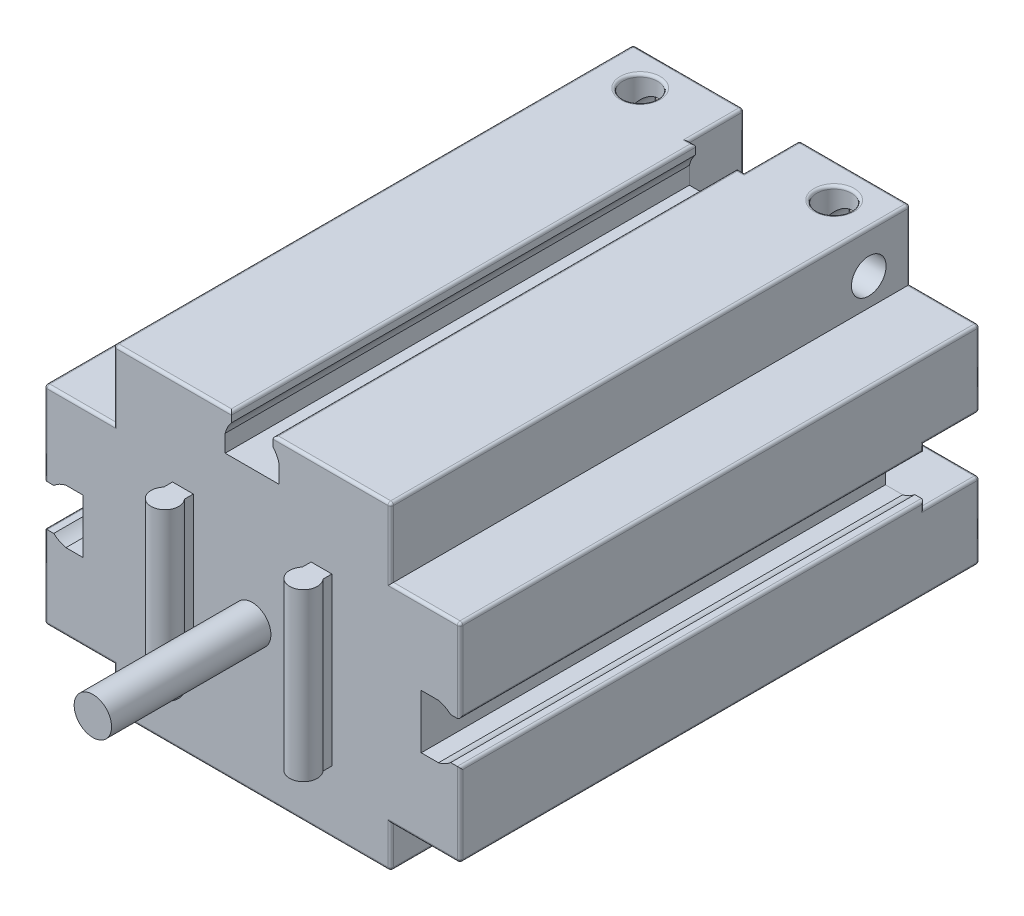
SolidWorks part; units mm, degrees
ref_plane "前视基准面" through (0, 0, 0) normal (0, 0, 1) x (1, 0, 0)
ref_plane "上视基准面" through (0, 0, 0) normal (0, 1, 0) x (1, 0, 0)
ref_plane "右视基准面" through (0, 0, 0) normal (1, 0, 0) x (0, 0, -1)
sketch "草图1" plane through (0, 0, 0) normal (0, 0, 1) x (1, 0, 0)
  line L0 (-15, 3) -> (-10, 3)
  line L1 (-10, 0) -> (10, 0)
  line L2 (-15, 3) -> (-15, 18)
  line L3 (-10, 23) -> (10, 23)
  line L4 (15, 3) -> (15, 18)
  line L5 (-10, 3) -> (-10, 0)
  line L6 (15, 3) -> (10, 3)
  line L7 (10, 3) -> (10, 0)
  line L8 (-10, 23) -> (-10, 18)
  line L9 (-10, 18) -> (-15, 18)
  line L10 (10, 23) -> (10, 18)
  line L11 (10, 18) -> (15, 18)
extrude "凸台-拉伸1" add sketch "草图1" against normal blind 37.5
sketch "草图3" plane through (0, 0, -37.5) normal (0, 0, -1) x (-1, 0, 0)
  line L0 (-15, 3) -> (-15, 18) construction
  line L1 (-15, 12.5) -> (-11, 12.5)
  line L2 (-15, 12.5) -> (-15, 8.5)
  line L3 (-15, 8.5) -> (-11, 8.5)
  line L4 (-11, 12.5) -> (-11, 8.5)
  line L5 (0, 24.5231) -> (0, -1.6726) construction
  line L6 (11, 12.5) -> (11, 8.5)
  line L7 (15, 8.5) -> (11, 8.5)
  line L8 (15, 12.5) -> (15, 8.5)
  line L9 (15, 12.5) -> (11, 12.5)
  line L10 (-10, 23) -> (10, 23) construction
  line L11 (-2, 23) -> (2, 23)
  line L12 (-2, 23) -> (-2, 19)
  line L13 (-2, 19) -> (2, 19)
  line L14 (2, 23) -> (2, 19)
extrude "切除-拉伸1" cut sketch "草图3" against normal blind 4
sketch "草图4" plane through (0, 0, 0) normal (0, 0, 1) x (1, 0, 0)
  line L0 (-1.5, 23) -> (-1.5, 22.3229)
  line L1 (10, 23) -> (-10, 23) construction
  line L2 (1.5, 23) -> (1.5, 22.3229)
  line L3 (-1.95, 20.2) -> (1.95, 20.2)
  line L4 (-1.95, 20.2) -> (-1.95, 21.4444)
  line L5 (1.95, 20.2) -> (1.95, 21.4444)
  line L6 (-1.5, 23) -> (1.5, 23)
  line L7 (-15, 9) -> (-14.3229, 9)
  line L8 (-15, 18) -> (-15, 3) construction
  line L9 (-15, 12) -> (-14.3229, 12)
  line L10 (-12.2, 8.55) -> (-13.4444, 8.55)
  line L11 (-12.2, 12.45) -> (-13.4444, 12.45)
  line L12 (-15, 9) -> (-15, 12)
  line L13 (-12.2, 8.55) -> (-12.2, 12.45)
  line L14 (0, 23.968) -> (0, -1.0844) construction
  line L15 (12.2, 8.55) -> (12.2, 12.45)
  line L16 (15, 9) -> (15, 12)
  line L17 (12.2, 12.45) -> (13.4444, 12.45)
  line L18 (12.2, 8.55) -> (13.4444, 8.55)
  line L19 (15, 12) -> (14.3229, 12)
  line L20 (15, 9) -> (14.3229, 9)
  arc A0 (-1.5, 22.3229) -> (-1.95, 21.4444) centre (0, 21) ccw
  arc A1 (1.95, 21.4444) -> (1.5, 22.3229) centre (0, 21) ccw
  arc A2 (-13.4444, 12.45) -> (-14.3229, 12) centre (-13, 10.5) ccw
  arc A3 (-14.3229, 9) -> (-13.4444, 8.55) centre (-13, 10.5) ccw
  arc A4 (14.3229, 9) -> (13.4444, 8.55) centre (13, 10.5) cw
  arc A5 (13.4444, 12.45) -> (14.3229, 12) centre (13, 10.5) cw
extrude "切除-拉伸2" cut sketch "草图4" against normal through all
sketch "草图5" plane through (11, 0, 0) normal (1, 0, 0) x (0, 0, -1)
  line L0 (37.5, 12) -> (36.8229, 12)
  line L1 (37.5, 9) -> (36.8229, 9)
  line L2 (37.5, 12) -> (37.5, 9)
  line L3 (37.5, 8.5) -> (37.5, 12.5) construction
  line L4 (34.7, 12.45) -> (35.9444, 12.45)
  line L5 (34.7, 8.55) -> (35.9444, 8.55)
  line L6 (34.7, 12.45) -> (34.7, 8.55)
  arc A0 (36.8229, 12) -> (35.9444, 12.45) centre (35.5, 10.5) ccw
  arc A1 (35.9444, 8.55) -> (36.8229, 9) centre (35.5, 10.5) ccw
extrude "切除-拉伸3" cut sketch "草图5" against normal up to next
sketch "草图6" plane through (0, 0, 0) normal (0, 0, 1) x (1, 0, 0)
  circle A0 centre (0, 10.5) radius 1.35
extrude "凸台-拉伸2" add sketch "草图6" along normal blind 11.5
sketch "草图7" plane through (0, 0, 0) normal (0, 1, 0) x (1, 0, 0)
  line L0 (-5.75, -0.6386) -> (-5.75, 0)
  line L1 (-10, 0) -> (10, 0) construction
  line L2 (0, 3.0305) -> (0, -5.9774) construction
  line L3 (-4.25, -0.6386) -> (-4.25, 0)
  line L4 (-4.25, 0) -> (-5.75, 0)
  line L5 (4.25, 0) -> (5.75, 0)
  line L6 (4.25, -0.6386) -> (4.25, 0)
  line L7 (5.75, -0.6386) -> (5.75, 0)
  arc A0 (-5.75, -0.6386) -> (-4.25, -0.6386) centre (-5, -1.3) ccw
  arc A1 (5.75, -0.6386) -> (4.25, -0.6386) centre (5, -1.3) cw
extrude "凸台-拉伸3" add sketch "草图7" along normal blind 12 from offset 4.5
sketch "草图8" plane through (0, 23, 0) normal (0, 1, 0) x (-1, 0, 0)
  circle A0 centre (7, -35) radius 1.25
  circle A1 centre (-7, -35) radius 1.25
extrude "切除-拉伸4" cut sketch "草图8" against normal blind 5
sketch "草图9" plane through (0, 0, -37.5) normal (0, 0, -1) x (-1, 0, 0)
  circle A0 centre (-7, 20.5) radius 1.25
  circle A1 centre (7, 20.5) radius 1.25
extrude "切除-拉伸5" cut sketch "草图9" against normal blind 5
sketch "草图10" plane through (-10, 0, 0) normal (-1, 0, 0) x (0, 0, 1)
  circle A0 centre (-34.5, 20) radius 1.25
extrude "切除-拉伸6" cut sketch "草图10" against normal blind 5
sketch "草图11" plane through (10, 0, 0) normal (1, 0, 0) x (0, 0, -1)
  circle A0 centre (34.5, 20) radius 1.25
extrude "切除-拉伸7" cut sketch "草图11" against normal blind 5
fillet "圆角1" radius 0.2 42 edges at (15, 15, 0) (15, 18, -18.75) (15, 15.25, -37.5) (15, 12.5, -35.5) (15, 12.25, -33.5) (15, 12, -16.75) (15, 8.75, -33.5) (15, 8.5, -35.5) (15, 5.75, -37.5) (15, 3, -18.75) (15, 6, 0) (15, 9, -16.75) (10, 0, -18.75) (0, 0, -37.5) (-10, 0, -18.75) (0, 0, 0) (-15, 6, 0) (-15, 3, -18.75) (-15, 5.75, -37.5) (-15, 8.5, -35.5) (-15, 8.75, -33.5) (-15, 9, -16.75) (-15, 12.25, -33.5) (-15, 12.5, -35.5) (-15, 15.25, -37.5) (-15, 18, -18.75) (-15, 15, 0) (-15, 12, -16.75) (-5.75, 23, 0) (-10, 23, -18.75) (-6, 23, -37.5) (-2, 23, -35.5) (-1.75, 23, -33.5) (-1.5, 23, -16.75) (-7, 23, -33.75) (1.75, 23, -33.5) (2, 23, -35.5) (6, 23, -37.5) (10, 23, -18.75) (5.75, 23, 0) (1.5, 23, -16.75) (7, 23, -33.75)
fillet "圆角2" radius 0.2 32 edges at (-9.9414, 22.9414, -37.4414) (-14.9414, 17.9414, -37.4414) (-14.9414, 3.0586, -37.4414) (-9.9414, 0.0586, -37.4414) (9.9414, 0.0586, -37.4414) (14.9414, 3.0586, -37.4414) (14.9414, 17.9414, -37.4414) (9.9414, 22.9414, -37.4414) (-9.9414, 0.0586, -0.0586) (-14.9414, 3.0586, -0.0586) (-14.9414, 17.9414, -0.0586) (-9.9414, 22.9414, -0.0586) (9.9414, 0.0586, -0.0586) (14.9414, 3.0586, -0.0586) (14.9414, 17.9414, -0.0586) (9.9414, 22.9414, -0.0586) (-10, 20.4, -37.5) (-12.4, 18, -37.5) (-12.4, 3, -37.5) (-10, 1.6, -37.5) (10, 1.6, -37.5) (12.4, 3, -37.5) (12.4, 18, -37.5) (10, 20.4, -37.5) (-10, 1.6, 0) (-12.4, 3, 0) (-12.4, 18, 0) (-10, 20.4, 0) (10, 1.6, 0) (12.4, 3, 0) (12.4, 18, 0) (10, 20.4, 0)
fillet "圆角3" radius 0.2 21 edges at (14.9414, 8.4414, -37.4414) (-14.9414, 8.4414, -37.4414) (-14.9414, 12.5586, -37.4414) (14.9414, 12.5586, -37.4414) (2.0586, 22.9414, -37.4414) (-2.0586, 22.9414, -37.4414) (12.9, 8.5, -37.5) (11, 8.75, -37.5) (0, 9, -37.5) (-11, 8.75, -37.5) (-12.9, 8.5, -37.5) (-12.9, 12.5, -37.5) (-11, 12.25, -37.5) (0, 12, -37.5) (11, 12.25, -37.5) (12.9, 12.5, -37.5) (2, 20.9, -37.5) (0, 19, -37.5) (-2, 20.9, -37.5) (5.75, 20.5, -37.5) (-8.25, 20.5, -37.5)
